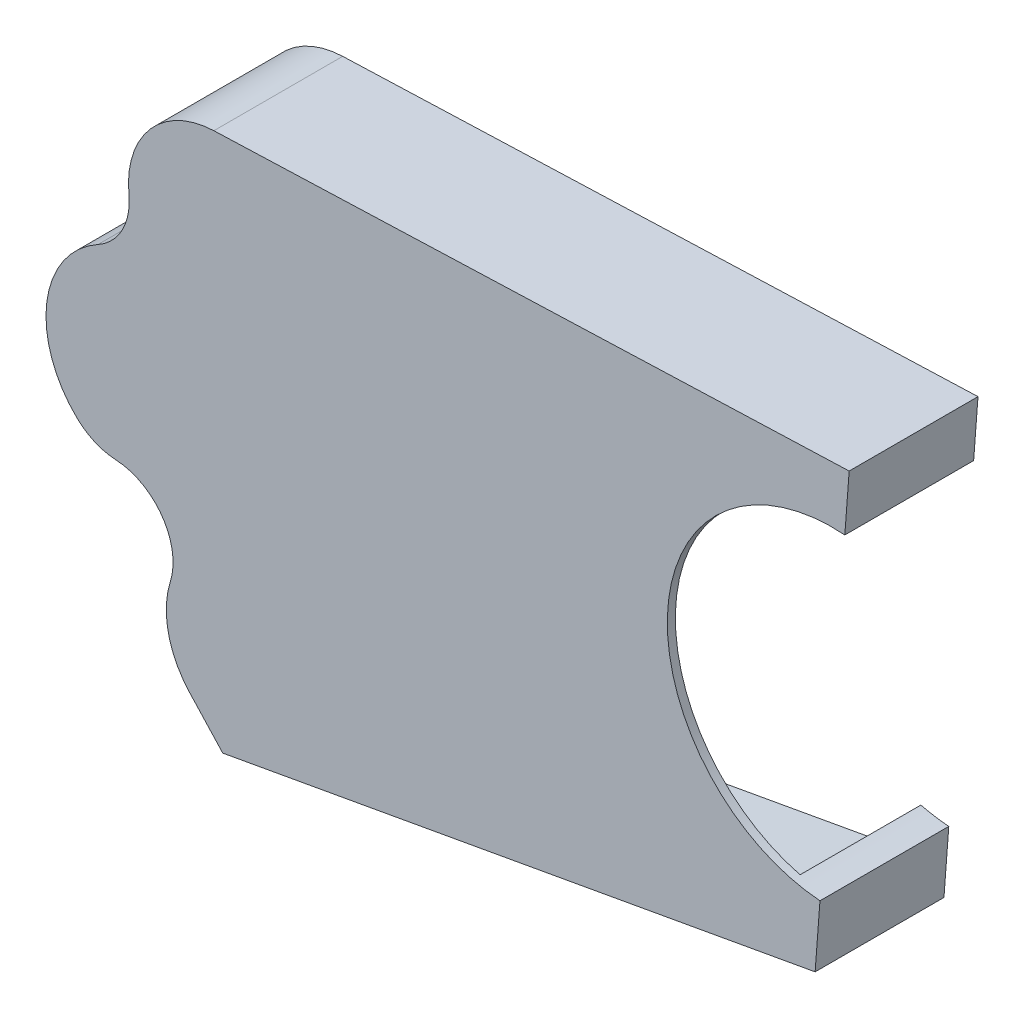
SolidWorks part; units mm, degrees
material "PLA 3D print"
ref_plane "Front Plane" through (0, 0, 0) normal (0, 0, 1) x (1, 0, 0)
ref_plane "Top Plane" through (0, 0, 0) normal (0, 1, 0) x (1, 0, 0)
ref_plane "Right Plane" through (0, 0, 0) normal (1, 0, 0) x (0, 0, -1)
sketch "Sketch1" plane through (0, 0, 0) normal (0, 0, 1) x (1, 0, 0)
  line L8 (-119.5948, -74.4106) -> (-92.5405, -103.7404)
  line L9 (-119.5948, -74.4106) -> (-92.5405, -103.7404)
  line L10 (-71.3446, -104.5958) -> (-37.2211, -73.1197)
  line L11 (-71.3446, -104.5958) -> (-37.2211, -73.1197)
  line L16 (-27.1401, -68.1042) -> (68.9251, -50.7959)
  line L17 (-111.4072, -83.2869) -> (68.9251, -50.7959)
  line L18 (56.0883, 55.6165) -> (-113.6124, 49.4857)
  line L19 (56.0883, 55.6165) -> (-113.6124, 49.4857)
  line L20 (-114.4495, -69.6645) -> (-87.3952, -98.9943)
  line L21 (-114.4495, -69.6645) -> (-87.3952, -98.9943)
  line L22 (-76.0907, -99.4505) -> (-41.9673, -67.9744)
  line L23 (-76.0907, -99.4505) -> (-41.9673, -67.9744)
  line L28 (-28.3813, -61.2151) -> (67.6838, -43.9068)
  line L29 (-108.8671, -75.7165) -> (67.6838, -43.9068)
  line L30 (56.341, 48.621) -> (-113.3597, 42.4902)
  line L31 (56.341, 48.621) -> (-113.3597, 42.4902)
  line L32 (44.1846, 55.1864) -> (35.7309, -56.7765)
  line L33 (-27.1401, -68.1042) -> (68.9251, -50.7959) construction
  line L34 (-113.6124, 49.4857) -> (56.0883, 55.6165) construction
  line L35 (-111.6252, 43.3) -> (42.409, 31.6699) construction
  line L36 (36.6151, 47.9084) -> (29.1586, -50.848)
  arc A22 (-124.4228, -52.9336) -> (-137.9704, -33.4802) centre (-138.7403, -48.4604) ccw
  arc A23 (-124.4228, -52.9336) -> (-137.9704, -33.4802) centre (-138.7403, -48.4604) ccw
  arc A24 (-124.4228, -52.9336) -> (-119.5948, -74.4106) centre (-103.4238, -59.4942) ccw
  arc A25 (-124.4228, -52.9336) -> (-119.5948, -74.4106) centre (-103.4238, -59.4942) ccw
  arc A26 (-92.5405, -103.7404) -> (-71.3446, -104.5958) centre (-81.5148, -93.5701) ccw
  arc A27 (-92.5405, -103.7404) -> (-71.3446, -104.5958) centre (-81.5148, -93.5701) ccw
  arc A28 (-27.1401, -68.1042) -> (-37.2211, -73.1197) centre (-23.5699, -87.9191) ccw
  arc A29 (-27.1401, -68.1042) -> (-37.2211, -73.1197) centre (-23.5699, -87.9191) ccw
  arc A30 (68.9251, -50.7959) -> (91, -33.5) centre (63.6055, -21.2712) ccw
  arc A31 (68.9251, -50.7959) -> (91, -33.5) centre (63.6055, -21.2712) ccw
  arc A32 (91, -33.5) -> (80.2612, 44.7896) centre (22.6589, -2.9929) ccw
  arc A44 (91, -33.5) -> (80.2612, 44.7896) centre (22.6589, -2.9929) ccw
  arc A45 (80.2612, 44.7896) -> (56.0883, 55.6165) centre (57.1714, 25.636) ccw
  arc A46 (80.2612, 44.7896) -> (56.0883, 55.6165) centre (57.1714, 25.636) ccw
  arc A47 (-113.6124, 49.4857) -> (-134.7058, 25.2795) centre (-112.8181, 27.5) ccw
  arc A48 (-113.6124, 49.4857) -> (-134.7058, 25.2795) centre (-112.8181, 27.5) ccw
  arc A49 (-142.3827, 10.6321) -> (-134.7058, 25.2795) centre (-149.6292, 23.7656) ccw
  arc A50 (-142.3827, 10.6321) -> (-134.7058, 25.2795) centre (-149.6292, 23.7656) ccw
  arc A51 (-142.3827, 10.6321) -> (-147.5429, -29.3643) centre (-130.3054, -11.2571) ccw
  arc A52 (-142.3827, 10.6321) -> (-147.5429, -29.3643) centre (-130.3054, -11.2571) ccw
  arc A53 (-147.5429, -29.3643) -> (-137.9704, -33.4802) centre (-137.2004, -18.5) ccw
  arc A54 (-147.5429, -29.3643) -> (-137.9704, -33.4802) centre (-137.2004, -18.5) ccw
  arc A55 (-117.7413, -55.0211) -> (-137.611, -26.4895) centre (-138.7403, -48.4604) ccw
  arc A56 (-117.7413, -55.0211) -> (-137.611, -26.4895) centre (-138.7403, -48.4604) ccw
  arc A57 (-117.7413, -55.0211) -> (-114.4495, -69.6645) centre (-103.4238, -59.4942) ccw
  arc A58 (-117.7413, -55.0211) -> (-114.4495, -69.6645) centre (-103.4238, -59.4942) ccw
  arc A59 (-87.3952, -98.9943) -> (-76.0907, -99.4505) centre (-81.5148, -93.5701) ccw
  arc A60 (-87.3952, -98.9943) -> (-76.0907, -99.4505) centre (-81.5148, -93.5701) ccw
  arc A61 (-28.3813, -61.2151) -> (-41.9673, -67.9744) centre (-23.5699, -87.9191) ccw
  arc A62 (-28.3813, -61.2151) -> (-41.9673, -67.9744) centre (-23.5699, -87.9191) ccw
  arc A63 (67.6838, -43.9068) -> (84.608, -30.6466) centre (63.6055, -21.2712) ccw
  arc A73 (67.6838, -43.9068) -> (84.608, -30.6466) centre (63.6055, -21.2712) ccw
  arc A74 (84.608, -30.6466) -> (74.8736, 40.3204) centre (22.6589, -2.9929) ccw
  arc A75 (84.608, -30.6466) -> (74.8736, 40.3204) centre (22.6589, -2.9929) ccw
  arc A76 (74.8736, 40.3204) -> (56.341, 48.621) centre (57.1714, 25.636) ccw
  arc A77 (74.8736, 40.3204) -> (56.341, 48.621) centre (57.1714, 25.636) ccw
  arc A78 (-113.3597, 42.4902) -> (-127.7415, 25.986) centre (-112.8181, 27.5) ccw
  arc A79 (-113.3597, 42.4902) -> (-127.7415, 25.986) centre (-112.8181, 27.5) ccw
  arc A80 (-139.0011, 4.5031) -> (-127.7415, 25.986) centre (-149.6292, 23.7656) ccw
  arc A81 (-139.0011, 4.5031) -> (-127.7415, 25.986) centre (-149.6292, 23.7656) ccw
  arc A82 (-139.0011, 4.5031) -> (-142.7164, -24.2943) centre (-130.3054, -11.2571) ccw
  arc A83 (-139.0011, 4.5031) -> (-142.7164, -24.2943) centre (-130.3054, -11.2571) ccw
  arc A84 (-142.7164, -24.2943) -> (-137.611, -26.4895) centre (-137.2004, -18.5) ccw
  arc A85 (-142.7164, -24.2943) -> (-137.611, -26.4895) centre (-137.2004, -18.5) ccw
  circle A86 centre (40.0178, 0) radius 41
  arc A87 (28.1249, 38.1911) -> (0.393, 5.4659) centre (40.0178, 0) ccw construction
  dimension "D4" = 1
  dimension "D3" = 7
  dimension "D1" = 0
  dimension "D2" = 7
extrude "Boss-Extrude1" add sketch "Sketch1" along normal blind 30 contours A52 A54 A23 A25 L9 A27 L11 A29 L17 A31 A44 A46 L19 A48 A50 A85 A83 A81 A79 L31 A77 A75 A73 L29 A62 L23 A60 L21 A58 A56 | A62 L29 L21 L17 L23 | L29 A62 L23 L17 L32 | A86 L36 L29 L32 | A86 L32 L31 L36 region at (-122.5189, -63.7868, 0) region at (-72.9993, -72.6407, 0) region at (-2.1687, -60.1476, 0) region at (32.9424, -45.3152, 0) region at (39.8821, 44.4918, 0)
sketch "Sketch3" plane through (0, 0, 30) normal (0, 0, 1) x (1, 0, 0)
  line L0 (-65.2656, 44.2277) -> (121.4688, -34.2162)
  line L1 (-113.3597, 42.4902) -> (36.6151, 47.9084) construction
  line L2 (29.1586, -50.848) -> (-108.8671, -75.7165) construction
  dimension "D1" = 33
sketch "Sketch4" plane through (0, 0, 30) normal (0, 0, 1) x (1, 0, 0)
  line L10 (-113.3597, 42.4902) -> (36.6151, 47.9084)
  line L11 (-113.3597, 42.4902) -> (36.6151, 47.9084)
  line L12 (36.6151, 47.9084) -> (36.0792, 40.8104)
  line L13 (36.6151, 47.9084) -> (36.0792, 40.8104)
  line L14 (43.1047, 40.8836) -> (44.1846, 55.1864)
  line L15 (43.1047, 40.8836) -> (44.1846, 55.1864)
  line L16 (35.7309, -56.7765) -> (36.9309, -40.8836)
  line L17 (35.7309, -56.7765) -> (36.9309, -40.8836)
  line L18 (29.9961, -39.7563) -> (29.1586, -50.848)
  line L19 (29.9961, -39.7563) -> (29.1586, -50.848)
  line L20 (29.1586, -50.848) -> (-108.8671, -75.7165)
  line L21 (29.1586, -50.848) -> (-108.8671, -75.7165)
  line L22 (-108.8671, -75.7165) -> (-114.4495, -69.6645)
  line L23 (-108.8671, -75.7165) -> (-114.4495, -69.6645)
  line L24 (44.1846, 55.1864) -> (-113.6124, 49.4857)
  line L25 (-119.5948, -74.4106) -> (-111.4072, -83.2869)
  line L26 (-111.4072, -83.2869) -> (35.7309, -56.7765)
  line L34 (44.1846, 55.1864) -> (-113.6124, 49.4857)
  line L35 (-119.5948, -74.4106) -> (-111.4072, -83.2869)
  line L36 (-111.4072, -83.2869) -> (35.7309, -56.7765)
  circle A14 centre (40.0178, 0) radius 41
  arc A15 (-142.7164, -24.2943) -> (-137.611, -26.4895) centre (-137.2004, -18.5) ccw
  arc A16 (-142.7164, -24.2943) -> (-137.611, -26.4895) centre (-137.2004, -18.5) ccw
  arc A17 (-139.0011, 4.5031) -> (-142.7164, -24.2943) centre (-130.3054, -11.2571) ccw
  arc A18 (-139.0011, 4.5031) -> (-142.7164, -24.2943) centre (-130.3054, -11.2571) ccw
  arc A19 (-139.0011, 4.5031) -> (-127.7415, 25.986) centre (-149.6292, 23.7656) ccw
  arc A20 (-139.0011, 4.5031) -> (-127.7415, 25.986) centre (-149.6292, 23.7656) ccw
  arc A21 (-113.3597, 42.4902) -> (-127.7415, 25.986) centre (-112.8181, 27.5) ccw
  arc A22 (-113.3597, 42.4902) -> (-127.7415, 25.986) centre (-112.8181, 27.5) ccw
  arc A23 (29.9961, -39.7563) -> (36.9309, -40.8836) centre (40.0178, 0) ccw
  arc A24 (29.9961, -39.7563) -> (36.9309, -40.8836) centre (40.0178, 0) ccw
  arc A25 (-117.7413, -55.0211) -> (-114.4495, -69.6645) centre (-103.4238, -59.4942) ccw
  arc A26 (-117.7413, -55.0211) -> (-114.4495, -69.6645) centre (-103.4238, -59.4942) ccw
  arc A27 (-117.7413, -55.0211) -> (-137.611, -26.4895) centre (-138.7403, -48.4604) ccw
  arc A28 (-117.7413, -55.0211) -> (-137.611, -26.4895) centre (-138.7403, -48.4604) ccw
  arc A32 (43.1047, 40.8836) -> (36.0792, 40.8104) centre (40.0178, 0) ccw
  arc A33 (-113.6124, 49.4857) -> (-134.7058, 25.2795) centre (-112.8181, 27.5) ccw
  arc A34 (-142.3827, 10.6321) -> (-134.7058, 25.2795) centre (-149.6292, 23.7656) ccw
  arc A35 (-142.3827, 10.6321) -> (-147.5429, -29.3643) centre (-130.3054, -11.2571) ccw
  arc A36 (-147.5429, -29.3643) -> (-137.9704, -33.4802) centre (-137.2004, -18.5) ccw
  arc A37 (-124.4228, -52.9336) -> (-137.9704, -33.4802) centre (-138.7403, -48.4604) ccw
  arc A38 (-124.4228, -52.9336) -> (-119.5948, -74.4106) centre (-103.4238, -59.4942) ccw
  arc A46 (43.1047, 40.8836) -> (36.0792, 40.8104) centre (40.0178, 0) ccw
  arc A47 (-113.6124, 49.4857) -> (-134.7058, 25.2795) centre (-112.8181, 27.5) ccw
  arc A48 (-142.3827, 10.6321) -> (-134.7058, 25.2795) centre (-149.6292, 23.7656) ccw
  arc A49 (-142.3827, 10.6321) -> (-147.5429, -29.3643) centre (-130.3054, -11.2571) ccw
  arc A50 (-147.5429, -29.3643) -> (-137.9704, -33.4802) centre (-137.2004, -18.5) ccw
  arc A51 (-124.4228, -52.9336) -> (-137.9704, -33.4802) centre (-138.7403, -48.4604) ccw
  arc A52 (-124.4228, -52.9336) -> (-119.5948, -74.4106) centre (-103.4238, -59.4942) ccw
  arc M25 (-137.611, -26.4895) -> (-142.7164, -24.2943) centre (-137.2004, -18.5) cw
  arc M26 (-142.7164, -24.2943) -> (-139.0011, 4.5031) centre (-130.3054, -11.2571) cw
  arc M27 (-139.0011, 4.5031) -> (-127.7415, 25.986) centre (-149.6292, 23.7656) ccw
  arc M28 (-127.7415, 25.986) -> (-113.3597, 42.4902) centre (-112.8181, 27.5) cw
  line M29 (-113.3597, 42.4902) -> (36.6151, 47.9084)
  line M30 (36.6151, 47.9084) -> (36.0792, 40.8104)
  arc M31 (36.0792, 40.8104) -> (43.1047, 40.8836) centre (40.0178, 0) cw
  line M32 (43.1047, 40.8836) -> (44.1846, 55.1864)
  line M33 (44.1846, 55.1864) -> (-113.6124, 49.4857)
  arc M34 (-113.6124, 49.4857) -> (-134.7058, 25.2795) centre (-112.8181, 27.5) ccw
  arc M35 (-134.7058, 25.2795) -> (-142.3827, 10.6321) centre (-149.6292, 23.7656) cw
  arc M36 (-142.3827, 10.6321) -> (-147.5429, -29.3643) centre (-130.3054, -11.2571) ccw
  arc M37 (-147.5429, -29.3643) -> (-137.9704, -33.4802) centre (-137.2004, -18.5) ccw
  arc M38 (-137.9704, -33.4802) -> (-124.4228, -52.9336) centre (-138.7403, -48.4604) cw
  arc M39 (-124.4228, -52.9336) -> (-119.5948, -74.4106) centre (-103.4238, -59.4942) ccw
  line M40 (-119.5948, -74.4106) -> (-111.4072, -83.2869)
  line M41 (-111.4072, -83.2869) -> (35.7309, -56.7765)
  line M42 (35.7309, -56.7765) -> (36.9309, -40.8836)
  arc M43 (36.9309, -40.8836) -> (29.9961, -39.7563) centre (40.0178, 0) cw
  line M44 (29.9961, -39.7563) -> (29.1586, -50.848)
  line M45 (29.1586, -50.848) -> (-108.8671, -75.7165)
  line M46 (-108.8671, -75.7165) -> (-114.4495, -69.6645)
  arc M47 (-114.4495, -69.6645) -> (-117.7413, -55.0211) centre (-103.4238, -59.4942) cw
  arc M48 (-117.7413, -55.0211) -> (-137.611, -26.4895) centre (-138.7403, -48.4604) ccw
  dimension "D1" = 0
extrude "Boss-Extrude2" add sketch "Sketch4" along normal blind 2 contours A14 M30 M29 M28 M27 M26 M25 M48 M47 M46 M45 M44 | M48 M25 M26 M27 M28 M29 M30 M31 M32 M33 M34 M35 M36 M37 M38 M39 M40 M41 M42 M43 M44 M45 M46 M47 region at (-125.9577, 38.9499, 30) region at (-60.3524, -9.964, 30)
